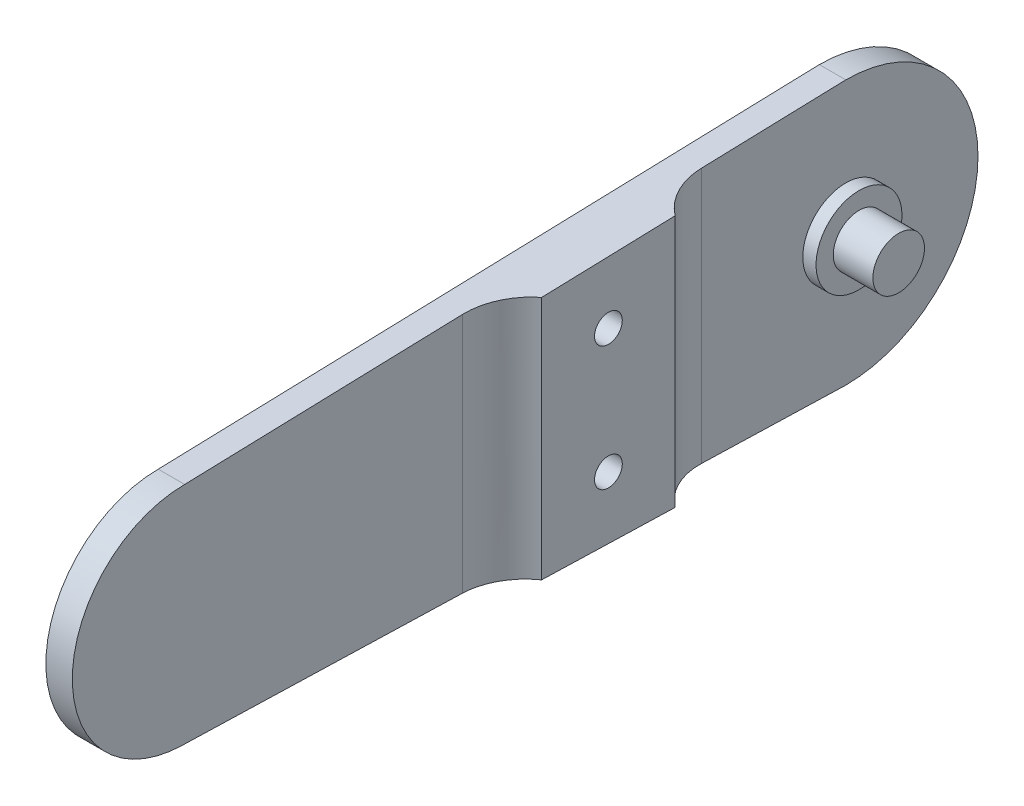
SolidWorks part; units mm, degrees
ref_plane "Front Plane" through (0, 0, 0) normal (1, 0, 0) x (0, 1, 0)
ref_plane "Top Plane" through (0, 0, 0) normal (0, 0, 1) x (0, 1, 0)
ref_plane "Right Plane" through (0, 0, 0) normal (0, 1, 0) x (-1, 0, 0)
sketch "Sketch1" plane through (0, 0, 0) normal (1, 0, 0) x (0, 1, 0)
  line L0 (0, 50) -> (0, -50) construction
  line L1 (-20, -50) -> (-16.9976, 50.2838)
  line L2 (20, -50) -> (17, 50)
  arc A0 (-20, -50) -> (20, -50) centre (0, -50) ccw
  arc A1 (17, 50) -> (-16.9976, 50.2838) centre (0, 50) ccw
  point P3 (0, 0)
  point P8 (0, 0)
  dimension "D2" = 17
  dimension "D3" = 20
  dimension "D1" = 100
extrude "Boss-Extrude1" add sketch "Sketch1" along normal blind 4
sketch "Sketch2" plane through (4, 0, 0) normal (1, 0, 0) x (0, 1, 0)
  circle A0 centre (0, -50) radius 3.9
  point P0 (0, -50)
  dimension "D1" = 7.8
extrude "Boss-Extrude2" add sketch "Sketch2" along normal blind 8
sketch "Sketch3" plane through (4, 0, 0) normal (1, 0, 0) x (0, 1, 0)
  circle A0 centre (0, -50) radius 6.5
  dimension "D1" = 13
extrude "Boss-Extrude3" add sketch "Sketch3" along normal blind 2
sketch "Sketch5" plane through (12, 0, 0) normal (1, 0, 0) x (0, 1, 0)
  line L0 (0, -50) -> (0, 0) construction
sketch "Sketch6" plane through (4, 0, 0) normal (1, 0, 0) x (0, 1, 0)
  line L0 (0, 0) -> (0, -20.1892) construction
  line L1 (0, 0) -> (18.5, 0)
  line L2 (0, 0) -> (-18.5031, 0)
  line L3 (20, -50) -> (17, 50)
  line L4 (-16.9976, 50.2838) -> (-20, -50)
  line L5 (19.1057, -20.1892) -> (18.5, 0)
  line L6 (-18.5031, 0) -> (-19.1075, -20.1892)
  line L7 (0, -20.1892) -> (19.1057, -20.1892)
  line L8 (0, -20.1892) -> (-19.1075, -20.1892)
  arc A2 (-20, -50) -> (20, -50) centre (0, -50) ccw
  arc A3 (17, 50) -> (-16.9976, 50.2838) centre (0, 50) ccw
  dimension "D1" = 0
extrude "Boss-Extrude4" add sketch "Sketch6" along normal blind 4
sketch "Sketch7" plane through (8, 0, 0) normal (1, 0, 0) x (0, 1, 0)
  line L0 (0, 0) -> (-0.0009, -20.1892) construction
  line L1 (-19.1075, -20.1892) -> (19.1057, -20.1892) construction
  line L2 (-0.0005, -10.0946) -> (18.8028, -10.0946) construction
  line L3 (19.1057, -20.1892) -> (18.5, 0) construction
  line L4 (-0.0005, -10.0946) -> (-18.8053, -10.0946) construction
  line L5 (-18.5031, 0) -> (-19.1075, -20.1892) construction
  circle A0 centre (-9.4029, -10.0946) radius 2.1
  circle A1 centre (9.4012, -10.0946) radius 2.1
  dimension "D1" = 4.2
extrude "Cut-Extrude1" cut sketch "Sketch7" against normal blind 4
fillet "Fillet1" radius 10 2 edges at (4, -0.0015, 0) (4, -0.0009, -20.1892)
